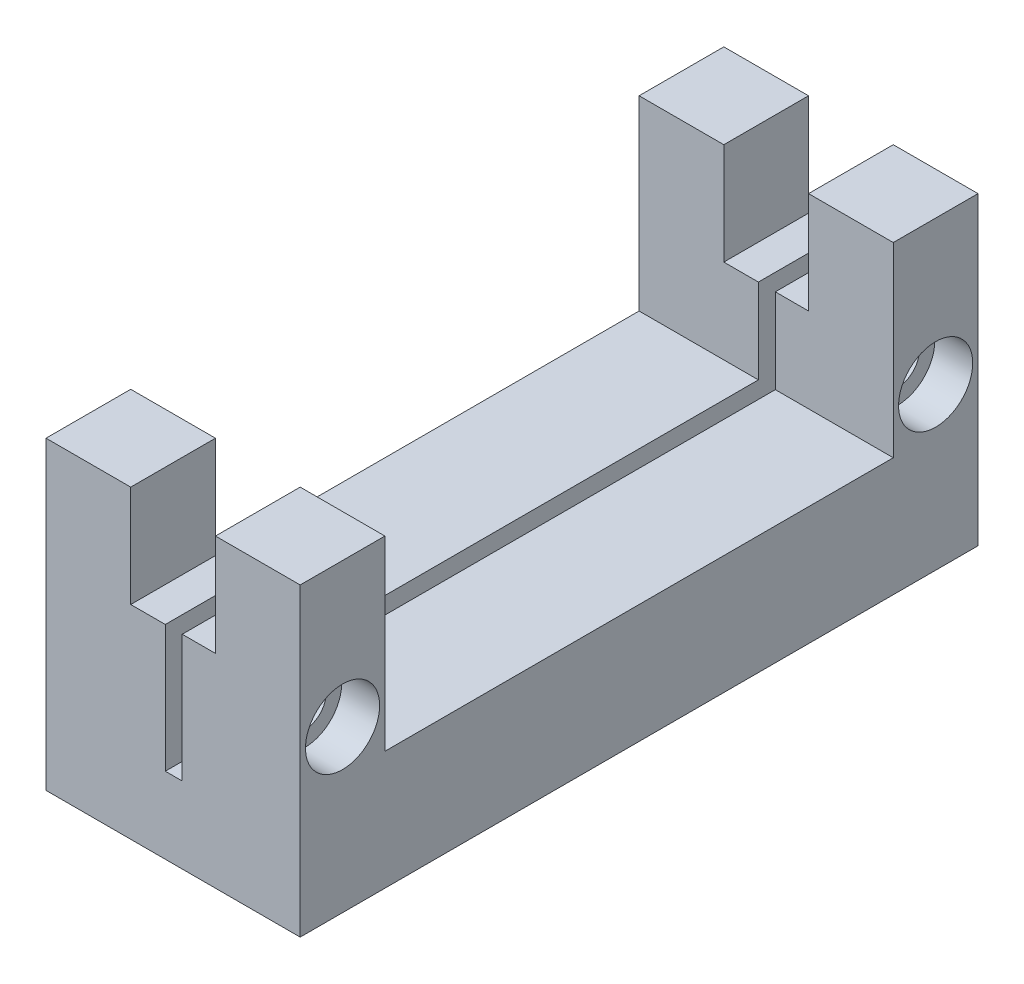
SolidWorks part; units mm, degrees
material "6061 Alloy"
ref_plane "Front Plane" through (0, 0, 0) normal (0, 0, 1) x (1, 0, 0)
ref_plane "Top Plane" through (0, 0, 0) normal (0, 1, 0) x (1, 0, 0)
ref_plane "Right Plane" through (0, 0, 0) normal (1, 0, 0) x (0, 0, -1)
sketch "Sketch2" plane through (0, 0, 0) normal (0, 0, 1) x (1, 0, 0)
  line L1 (-9.525, -9.525) -> (9.525, -9.525)
  line L2 (-9.525, -9.525) -> (-9.525, 9.525)
  line L3 (-9.525, 9.525) -> (9.525, 9.525)
  line L4 (9.525, -9.525) -> (9.525, 9.525)
  line L5 (-9.525, -9.525) -> (9.525, 9.525) construction
  line L6 (-9.525, 9.525) -> (9.525, -9.525) construction
  point P0 (0, 0)
  dimension "D1" = 19.05
  dimension "D2" = 19.05
extrude "Boss-Extrude1" add sketch "Sketch2" along normal mid plane 50.8
sketch "Sketch4" plane through (-1.5069, 3.1105, 25.4) normal (0, 0, 1) x (1, 0, 0)
  line L1 (-1.6681, 6.4145) -> (4.6819, 6.4145)
  line L2 (-1.6681, 6.4145) -> (-1.6681, -3.7455)
  line L3 (-1.6681, -3.7455) -> (4.6819, -3.7455)
  line L4 (4.6819, 6.4145) -> (4.6819, -3.7455)
  line L7 (-8.0181, 6.4145) -> (11.0319, 6.4145)
  line L8 (-8.0181, 6.4145) -> (-8.0181, 3.8745)
  line L9 (-8.0181, 3.8745) -> (11.0319, 3.8745)
  line L10 (11.0319, 6.4145) -> (11.0319, 3.8745)
  line L11 (11.0319, 6.4145) -> (-8.0181, 6.4145) construction
  line L12 (11.0319, -12.6355) -> (11.0319, 6.4145) construction
  line L13 (-8.0181, 6.4145) -> (-8.0181, -12.6355) construction
  dimension "D1" = 6.35
  dimension "D2" = 0
  dimension "D3" = 10.16
  dimension "D4" = 2.54
  dimension "D5" = 0
  dimension "D6" = 0
  dimension "D7" = 0
  dimension "D8" = 6.35
extrude "Cut-Extrude1" cut sketch "Sketch4" against normal through all contours L4 L9 | L2 L9 L4 | L9 L2 L3 L4 | L9 L2 region at (0, 8.255, 25.4) region at (-6.35, 8.255, 25.4) region at (6.35, 8.255, 25.4) region at (0, 3.175, 25.4)
sketch "Sketch7" plane through (9.525, 0, 0) normal (1, 0, 0) x (0, 0, -1)
  line L0 (25.4, 6.985) -> (-25.4, 6.985) construction
  line L1 (-19.05, 6.985) -> (19.05, 6.985)
  line L2 (-19.05, 6.985) -> (-19.05, -6.985)
  line L3 (-19.05, -6.985) -> (19.05, -6.985)
  line L4 (19.05, 6.985) -> (19.05, -6.985)
  line L5 (-25.4, -9.525) -> (-25.4, 6.985) construction
  line L6 (25.4, -9.525) -> (25.4, 6.985) construction
  line L7 (-25.4, -9.525) -> (25.4, -9.525) construction
  dimension "D1" = 6.35
  dimension "D2" = 6.35
  dimension "D3" = 2.54
extrude "Cut-Extrude3" cut sketch "Sketch7" against normal through all
sketch "Sketch8" plane through (0, 0, 25.4) normal (0, 0, 1) x (1, 0, 0)
  line L0 (-9.525, -9.525) -> (9.525, -9.525)
  line L1 (-9.525, -9.525) -> (-9.525, -15.875)
  line L2 (9.525, -9.525) -> (9.525, -15.875)
  line L3 (-9.525, -15.875) -> (9.525, -15.875)
  dimension "D1" = 6.35
extrude "Boss-Extrude2" add sketch "Sketch8" against normal up to surface (50.8 mm away) up to face at (0, 0.9525, -25.4)
sketch "Sketch11" plane through (0, 0, 25.4) normal (0, 0, 1) x (1, 0, 0)
  line L0 (-3.175, -0.635) -> (3.175, -0.635) construction
  line L1 (-0.5848, -0.635) -> (0.6852, -0.635)
  line L2 (-0.5848, -0.635) -> (-0.5848, -10.16)
  line L3 (-0.5848, -10.16) -> (0.6852, -10.16)
  line L4 (0.6852, -0.635) -> (0.6852, -10.16)
  line L5 (-0.5848, -0.635) -> (0.6852, -10.16) construction
  line L6 (-0.5848, -10.16) -> (0.6852, -0.635) construction
  point P0 (0.0502, -5.3975)
  dimension "D1" = 1.27
  dimension "D2" = 0
  dimension "D3" = 9.525
extrude "Cut-Extrude4" cut sketch "Sketch11" against normal through all
hole_wizard "CBORE for #4 Socket Head Cap Screw2" positions "Sketch12" profile "Sketch13" counterbore size "#4" standard "ANSI Inch" end condition up to next
sketch "Sketch12" plane through (9.525, 0, 0) normal (1, 0, 0) x (0, 0, -1)
  line L0 (-19.05, 6.985) -> (-19.05, -6.985) construction
  line L1 (19.05, -6.985) -> (19.05, 6.985) construction
  point P0 (-22.225, -3.81)
  point P2 (22.225, -3.81)
  dimension "D1" = 3.175
  dimension "D2" = 3.175
  dimension "D3" = 3.175
  dimension "D4" = 3.175
sketch "Sketch13" plane through (9.525, -3.81, 22.225) normal (0, 1, 0) x (0, 0, -1)
  line L0 (0, 0) -> (0, 8.8398)
  line L1 (0, 8.8398) -> (1.6319, 8.8398)
  line L3 (1.6319, 8.8398) -> (1.6319, 2.8448)
  line L4 (1.6319, 2.8448) -> (2.7788, 2.8448)
  line L5 (2.7788, 2.8448) -> (2.7788, 0)
  line L7 (2.7788, 0) -> (0, 0)
  line L11 (0, -6.35) -> (0, 107.95) construction
  dimension "Thru Hole Dia." = 3.2639
  dimension "Thru Hole Depth" = 8.8398
  dimension "C'Bore Dia." = 5.5575
  dimension "C'Bore Depth" = 2.8448
hole_wizard "#4-40 Tapped Hole1" positions "Sketch14" profile "Sketch15" tap size "#4-40" standard "ANSI Inch" end condition up to next
sketch "Sketch14" plane through (-0.5848, 0, 0) normal (1, 0, 0) x (0, 0, -1)
  point P0 (-22.225, -3.81)
  point P3 (22.225, -3.81)
sketch "Sketch15" plane through (-0.5848, -3.81, 22.225) normal (0, 1, 0) x (0, 0, -1)
  line L0 (0, 0) -> (0, 8.9402)
  line L1 (0, 8.9402) -> (1.1303, 8.9402)
  line L2 (1.1303, 8.9402) -> (1.1303, 0)
  line L5 (1.1303, 0) -> (0, 0)
  line L11 (0, -6.35) -> (0, 107.95) construction
  dimension "Thru Tap Drill Dia." = 2.2606
  dimension "Thru Tap Drill Depth" = 8.9402
cosmetic thread "Hole Thread1" parameters "D2"=2.8448
cosmetic thread "Hole Thread2" parameters "D2"=2.8448
hole_wizard "#4-40 Tapped Hole2" positions "Sketch16" profile "Sketch17" tap size "#4-40" standard "ANSI Inch" end condition up to next
sketch "Sketch16" plane through (0, -15.875, 0) normal (0, -1, 0) x (-1, 0, 0)
  line L0 (9.525, -25.4) -> (-9.525, -25.4) construction
  line L1 (9.525, 25.4) -> (-9.525, 25.4) construction
  point P0 (0, -22.225)
  point P2 (0, 22.225)
  dimension "D1" = 3.175
  dimension "D2" = 3.175
sketch "Sketch17" plane through (0, -15.875, 22.225) normal (1, 0, 0) x (0, 0, -1)
  line L0 (0, 0) -> (0, 5.715)
  line L1 (0, 5.715) -> (1.1303, 5.715)
  line L2 (1.1303, 5.715) -> (1.1303, 0)
  line L5 (1.1303, 0) -> (0, 0)
  line L11 (0, -6.35) -> (0, 107.95) construction
  dimension "Thru Tap Drill Dia." = 2.2606
  dimension "Thru Tap Drill Depth" = 5.715
cosmetic thread "Hole Thread3" parameters "D2"=2.8448
cosmetic thread "Hole Thread4" parameters "D2"=2.8448
